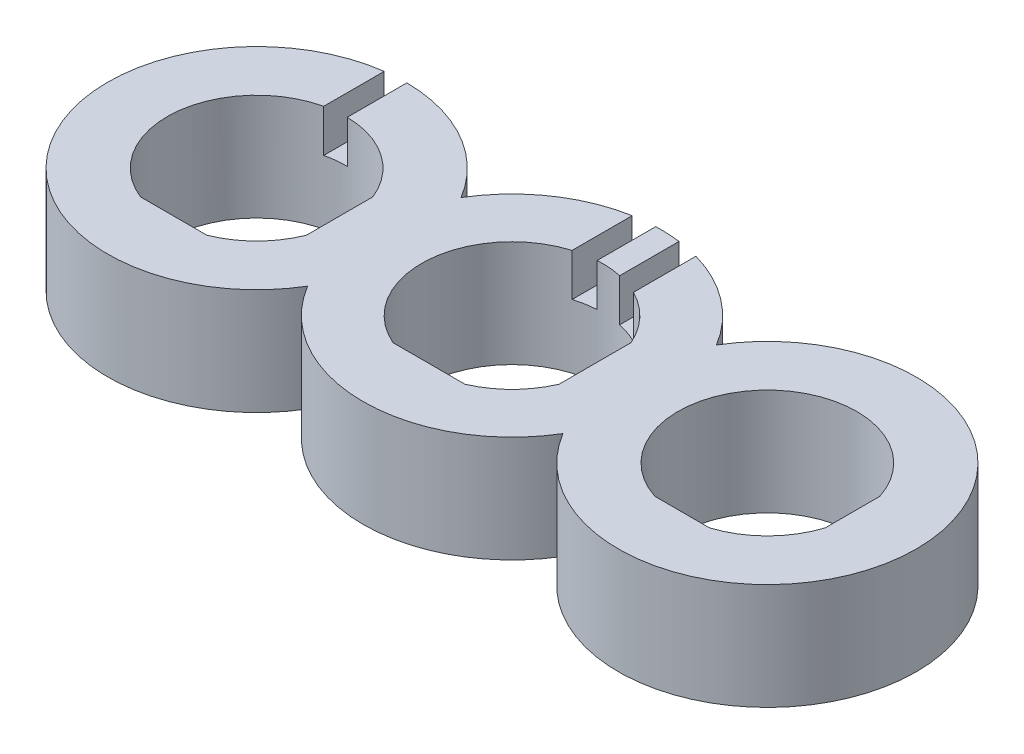
SolidWorks part; units mm, degrees
ref_plane "Спереди" through (0, 0, 0) normal (0, 0, 1) x (1, 0, 0)
ref_plane "Сверху" through (0, 0, 0) normal (0, 1, 0) x (1, 0, 0)
ref_plane "Справа" through (0, 0, 0) normal (1, 0, 0) x (0, 0, -1)
sketch "Эскиз1" plane through (0, 0, 0) normal (0, 1, 0) x (1, 0, 0)
  line L1 (3.9, -1.5588) -> (3.9, 1.5588)
  line L2 (1.5588, -3.9) -> (-1.5588, -3.9)
  circle A0 centre (0, 0) radius 4.2 construction
  circle A1 centre (0, 0) radius 7
  arc A2 (1.5588, -3.9) -> (3.9, -1.5588) centre (0, 0) ccw
  arc A3 (3.9, 1.5588) -> (-1.5588, -3.9) centre (0, 0) ccw
  dimension "D1" = 14
  dimension "D2" = 8.4
  dimension "D3" = 3.9
extrude "Вытянуть1" add sketch "Эскиз1" along normal blind 5
sketch "Эскиз2" plane through (0, 0, 0) normal (0, 1, 0) x (1, 0, 0)
  line L0 (15.9, 1.6889) -> (15.9, -1.6889)
  line L1 (10.3111, -3.9) -> (13.6889, -3.9)
  circle A0 centre (12, 0) radius 7
  circle A1 centre (12, 0) radius 4.25 construction
  arc A2 (15.9, 1.6889) -> (10.3111, -3.9) centre (12, 0) ccw
  arc A3 (13.6889, -3.9) -> (15.9, -1.6889) centre (12, 0) ccw
  dimension "D1" = 8.5
  dimension "D2" = 14
  dimension "D3" = 12
  dimension "D4" = 3.9
extrude "Вытянуть2" add sketch "Эскиз2" along normal blind 5
sketch "Эскиз3" plane through (0, 0, 0) normal (0, 1, 0) x (1, 0, 0)
  line L0 (28, 1.2806) -> (28, -1.2806)
  line L1 (25.2806, -4) -> (22.7194, -4)
  circle A0 centre (24, 0) radius 4.2 construction
  circle A1 centre (24, 0) radius 7
  arc A2 (28, 1.2806) -> (22.7194, -4) centre (24, 0) ccw
  arc A3 (28, -1.2806) -> (25.2806, -4) centre (24, 0) cw
  dimension "D1" = 8.4
  dimension "D2" = 14
  dimension "D3" = 24
  dimension "D4" = 4
extrude "Вытянуть3" add sketch "Эскиз3" along normal blind 5
sketch "Эскиз4" plane through (0, 5, 0) normal (0, 1, 0) x (1, 0, 0)
  line L1 (-0.941, 9.0252) -> (0.059, 9.0252)
  line L2 (-0.941, 9.0252) -> (-0.941, 2.2921)
  line L3 (-0.941, 2.2921) -> (0.059, 2.2921)
  line L4 (0.059, 9.0252) -> (0.059, 2.2921)
  line L5 (10.7584, 9.0252) -> (11.7584, 9.0252)
  line L6 (10.7584, 9.0252) -> (10.7584, 1.6713)
  line L7 (10.7584, 1.6713) -> (11.7584, 1.6713)
  line L8 (11.7584, 9.0252) -> (11.7584, 1.6713)
  line L9 (12.9073, 9.0252) -> (13.9073, 9.0252)
  line L10 (12.9073, 9.0252) -> (12.9073, 1.6713)
  line L11 (12.9073, 1.6713) -> (13.9073, 1.6713)
  line L12 (13.9073, 9.0252) -> (13.9073, 1.6713)
  dimension "D1" = 1
extrude "Вытянуть7" cut sketch "Эскиз4" against normal blind 2
